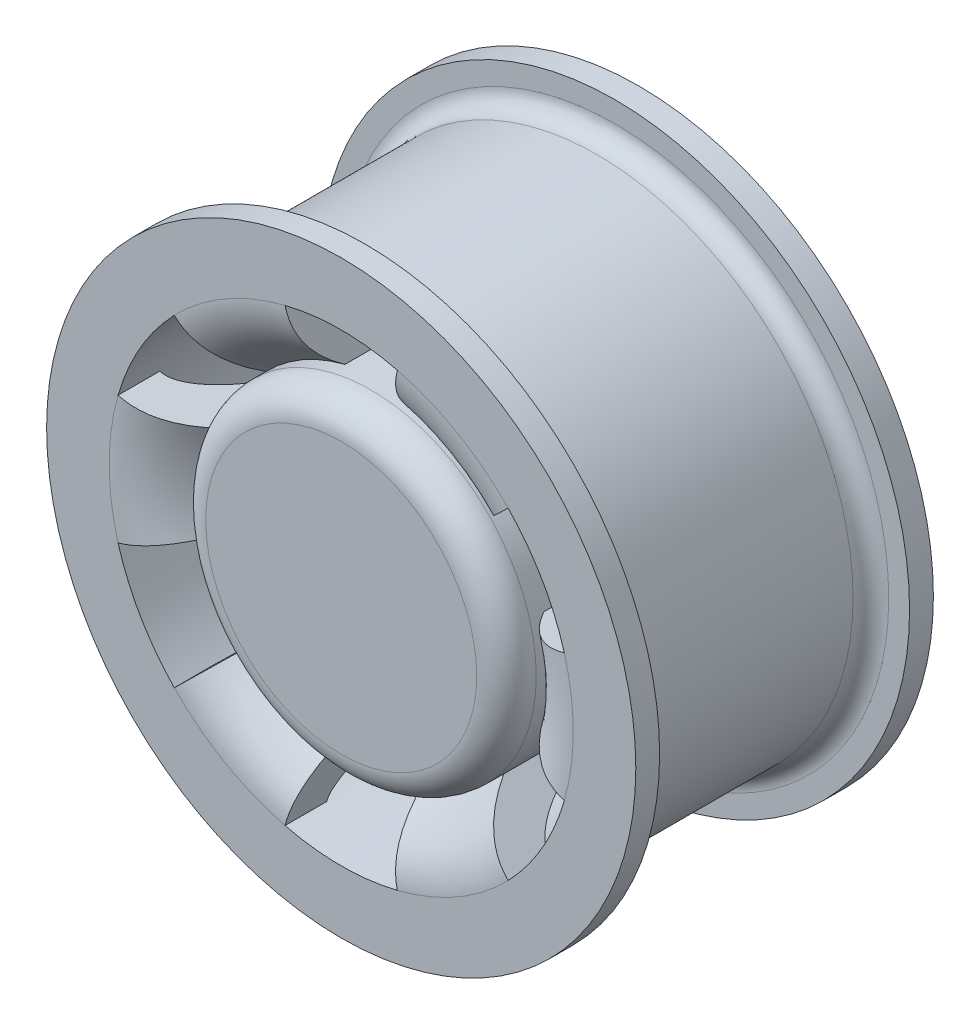
SolidWorks part; units mm, degrees
material "ABS"
ref_plane "Спереди" through (0, 0, 0) normal (0, 0, 1) x (1, 0, 0)
ref_plane "Сверху" through (0, 0, 0) normal (0, 1, 0) x (1, 0, 0)
ref_plane "Справа" through (0, 0, 0) normal (1, 0, 0) x (0, 0, -1)
sketch "Эскиз1" plane through (0, 0, 0) normal (0, 1, 0) x (1, 0, 0)
  line L0 (0, 0) -> (0, 47.4199) construction
  line L1 (0, 0) -> (79.812, 0) construction
  line L2 (39, 25) -> (39, -18)
  line L3 (39, -25) -> (47, -25)
  line L5 (49.5, -21) -> (46, -21)
  line L6 (43, -18) -> (43, 18)
  line L9 (39, 25) -> (47, 25)
  line L10 (40.0579, -25) -> (51.9421, -25) construction
  line L11 (20.5, 0) -> (27.7696, 0)
  line L13 (47, -25) -> (49.5, -25)
  line L14 (49.5, -25) -> (49.5, -21)
  line L15 (46, 21) -> (49.5, 21)
  line L16 (49.5, 21) -> (49.5, 25)
  line L17 (49.5, 25) -> (47, 25)
  arc A0 (46, -21) -> (43, -18) centre (46, -18) cw
  arc A1 (46, 21) -> (43, 18) centre (46, 18) ccw
  spline S0 degree 3 poles (39, -25) (27.4862, -25) (22.2386, -6.3236) (20.5, 0) knots 0 0 0 0 1 1 1 1
  spline S1 degree 1 poles (39, -18) (27.2495, 1.8557) knots 0 0 1 1 construction
  spline S2 degree 3 poles (39, -18) (38.7744, -18) (38.3151, -17.9532) (37.6952, -17.7601) (36.9533, -17.3777) (35.803, -16.5242) (34.1483, -14.7283) (32.1952, -11.6157) (30.4751, -7.9745) (29.2989, -4.8534) (28.5209, -2.5054) (28.0174, -0.8635) (27.6637, 0.3644) (27.4146, 1.2563) (27.3057, 1.6516) (27.2495, 1.8557) knots 0 0 0 0 0.0625 0.125 0.1875 0.25 0.375 0.5 0.625 0.75 0.8125 0.875 0.9375 0.96875 1 1 1 1 only from (39, -18) to (27.7696, 0)
  point P3 (43, 21)
  point P12 (43, -21)
  point P16 (43, 0)
  point P19 (39.005, 0)
  dimension "D5" = 3
  dimension "D1" = 25
  dimension "D2" = 8
  dimension "D3" = 3.5
  dimension "D4" = 4
  dimension "D6" = 43
  dimension "D7" = 20.5
  dimension "D8" = 28
  dimension "D10" = 18
  dimension "D11" = 7.2696
  dimension "D12" = 4
  dimension "D13" = 3.5
  dimension "D9" = 7
revolve "Повернуть1" add sketch "Эскиз1" angle 360 about L0
sketch "Эскиз2" plane through (0, 0, 0) normal (0, 0, -1) x (-1, 0, 0)
  circle A0 centre (0, 0) radius 20.5 construction
  circle A1 centre (0, 0) radius 27.7696 construction
  circle A2 centre (0, 0) radius 20.5
  circle A3 centre (0, 0) radius 27.7696
extrude "Бобышка-Вытянуть1" add sketch "Эскиз2" against normal through all
sketch "Эскиз3" plane through (0, 0, 25) normal (0, 0, 1) x (1, 0, 0)
  circle A0 centre (0, 0) radius 27.7696 construction
  circle A1 centre (0, 0) radius 27.7696
extrude "Бобышка-Вытянуть2" add sketch "Эскиз3" against normal blind 5
sketch "Эскиз4" plane through (0, 0, 25) normal (0, 0, 1) x (1, 0, 0)
  line L0 (-6.7181, 26.9447) -> (-9.435, 37.8415)
  line L1 (6.7181, 26.9447) -> (9.435, 37.8415)
  circle A0 centre (0, 0) radius 27.7696 construction
  arc A1 (6.7181, 26.9447) -> (-6.7181, 26.9447) centre (0, 0) ccw
  circle A2 centre (0, 0) radius 39 construction
  arc A3 (9.435, 37.8415) -> (-9.435, 37.8415) centre (0, 0) ccw
  dimension "D1" = 28
extrude "Вырез-Вытянуть1" cut sketch "Эскиз4" against normal through all
pattern_circular "Круговой массив1" count 6 over 360 about axis through (0, 0, 25) along (0, 0, -1) of "Вырез-Вытянуть1"
fillet "Скругление1" radius 5 1 edges at (-27.7696, 0, 25)
sketch3d "Трехмерный эскиз1"
  line L0 (0, 0, 0) -> (-27.7696, 0, 0) construction
  arc A0 (-26.6938, 7.6543, 0) -> (-26.6938, -7.6543, 0) centre (0, 0, 0) ccw construction
  point P6 (0, 0, 27.7696)
  point P7 (-23.75, 0, 0)
  dimension "D1" = 23.75
hole_wizard "Сверление под метчик M51" positions "Эскиз11" profile "Эскиз13" hole size "M5" standard "ISO"
sketch "Эскиз11" plane through (0, 0, 0) normal (0, 0, -1) x (-1, 0, 0)
  point P0 (23.75, 0)
sketch "Эскиз13" plane through (-23.75, 0, 0) normal (1, 0, 0) x (0, 1, 0)
  line L0 (0, 0) -> (0, 23.2618)
  line L1 (0, 23.2618) -> (2.1, 22)
  line L2 (2.1, 22) -> (2.1, 0)
  line L5 (2.1, 0) -> (0, 0)
  line L10 (0, 23.2618) -> (-2.1, 22) construction
  line L11 (0, -6.35) -> (0, 107.95) construction
  dimension "Диаметр отверстия" = 4.2
  dimension "Глубина отверстия" = 22
  dimension "Угол заточки сверла" = 118
cosmetic thread "Условное изображение резьбы1" parameters "D2"=5
pattern_circular "Круговой массив3" count 6 over 360 about axis through (0, 0, 25) along (0, 0, -1) of "Сверление под метчик M51" reverse direction yes
chamfer "Фаска2" distance 0.6 angle 45 6 edges at (-13.975, -20.5681, 0) (9.775, -20.5681, 0) (21.65, 0, 0) (9.775, 20.5681, 0) (-13.975, 20.5681, 0) (-25.85, 0, 0)
